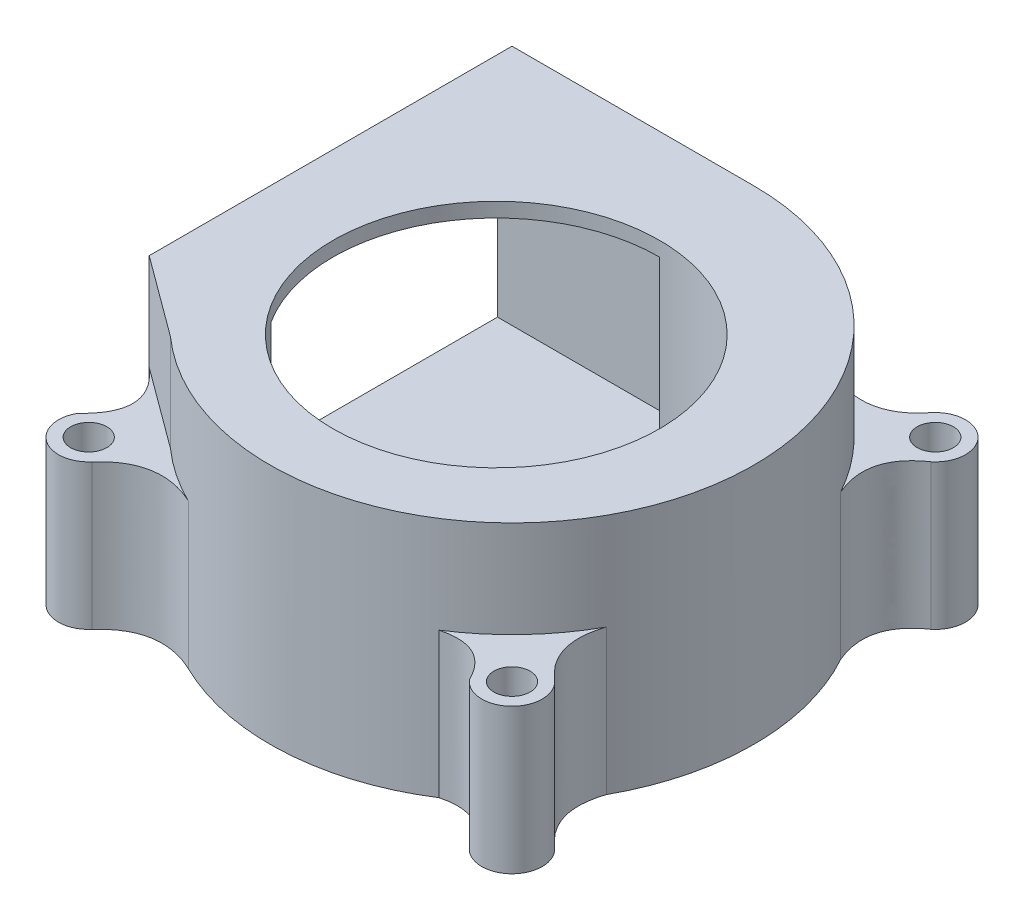
SolidWorks part; units mm, degrees
ref_plane "前视基准面" through (0, 0, 0) normal (0, 0, 1) x (1, 0, 0)
ref_plane "上视基准面" through (0, 0, 0) normal (0, 1, 0) x (1, 0, 0)
ref_plane "右视基准面" through (0, 0, 0) normal (1, 0, 0) x (0, 0, -1)
other "Configuration Table"
sketch "草图1" plane through (0, 0, 0) normal (0, 1, 0) x (1, 0, 0)
  line L1 (0, 0) -> (40, 0)
  line L2 (0, 0) -> (0, 40)
  line L3 (0, 40) -> (40, 40)
  line L4 (40, 0) -> (40, 40)
  circle A0 centre (2.5, 2.5) radius 1.5
  circle A1 centre (37.5, 2.5) radius 1.5
  circle A2 centre (37.5, 37.5) radius 1.5
  circle A4 centre (2.5, 37.5) radius 1.5 [skipped]
  dimension "D3" = 3
  dimension "D4" = 2.5
  dimension "D5" = 2.5
  dimension "D1" = 40
  dimension "D2" = 40
  dimension "D6" = 2
  dimension "D7" = 2
extrude "凸台-拉伸1" add sketch "草图1" along normal blind 20
sketch "草图2" plane through (0, 0, 0) normal (-1, 0, 0) x (0, 0, 1)
  line L0 (-40, 20) -> (-40, 0) construction
  line L1 (-11.5, 1.2) -> (-38.8, 1.2)
  line L2 (-11.5, 1.2) -> (-11.5, 18.8)
  line L3 (-11.5, 18.8) -> (-38.8, 18.8)
  line L4 (-38.8, 1.2) -> (-38.8, 18.8)
  line L5 (-40, 0) -> (0, 0) construction
  line L6 (-40, 20) -> (0, 20) construction
  dimension "D1" = 27.3
  dimension "D2" = 1.2
  dimension "D3" = 1.2
  dimension "D4" = 1.2
extrude "切除-拉伸1" cut sketch "草图2" against normal blind 20
sketch "草图3" plane through (0, 20, 0) normal (0, 1, 0) x (1, 0, 0)
  circle A0 centre (20, 18.7) radius 13.5
  circle A1 centre (2.5, 2.5) radius 1.5 construction
  circle A4 centre (37.5, 2.5) radius 1.5 construction
  point P8 (38.0337, 36.0982)
  dimension "D1" = 17.5
  dimension "D2" = 16.2
  dimension "D3" = 27
extrude "切除-拉伸2" cut sketch "草图3" against normal blind 18
sketch "草图4" plane through (0, 20, 0) normal (0, 1, 0) x (1, 0, 0)
  line L0 (20, 11.5) -> (20, 32.2) construction
  line L1 (20, 40) -> (0, 40)
  line L2 (0, 40) -> (0, 20)
  line L3 (0, 10) -> (6.6926, 5.0697)
  line L4 (0, 40) -> (0, 0) construction
  line L5 (0, 20) -> (0, 10)
  arc A0 (6.6926, 5.0697) -> (20, 40) centre (20, 20) ccw
  dimension "D1" = 30
extrude "切除-拉伸3" cut sketch "草图4" against normal blind 8 flip side to cut
sketch "草图5" plane through (0, 12, 0) normal (0, 1, 0) x (1, 0, 0)
  line L10 (0, 40) -> (0, 10)
  line L11 (20, 40) -> (0, 40)
  line L12 (0, 10) -> (6.6926, 5.0697)
  line L13 (0, 40) -> (0, 10)
  line L14 (20, 40) -> (0, 40)
  arc A0 (39.0764, 35.5597) -> (35.5993, 39.124) centre (37.5, 37.5) ccw
  arc A1 (35.5993, 0.876) -> (39.1801, 4.3513) centre (37.5, 2.5) ccw
  arc A2 (0.3398, 3.7584) -> (4.4007, 0.876) centre (2.5, 2.5) ccw
  arc A6 (37.5, 10.3175) -> (37.5, 29.6825) centre (20, 20) ccw
  arc A7 (6.6926, 5.0697) -> (20, 40) centre (20, 20) ccw
  arc A8 (11.2003, 2.0399) -> (30.7946, 3.1633) centre (20, 20) ccw
  arc A9 (29.6825, 37.5) -> (20, 40) centre (20, 20) ccw
  spline S0 degree 2 poles (0, 10) (3.6388, 6.8784) (0.3398, 3.7584) knots 0 0 0 1 1 1
  spline S1 degree 2 poles (11.2003, 2.0399) (7.1439, 3.9525) (4.4007, 0.876) knots 0 0 0 1 1 1
  spline S2 degree 2 poles (30.7946, 3.1633) (34.0639, 4.0359) (35.5993, 0.876) knots 0 0 0 1 1 1
  spline S3 degree 2 poles (37.5, 10.3175) (36.3198, 6.7657) (39.1801, 4.3513) knots 0 0 0 1 1 1
  spline S4 degree 2 poles (29.6825, 37.5) (33.3343, 36.2155) (35.5993, 39.124) knots 0 0 0 1 1 1
  spline S5 degree 2 poles (37.5, 29.6825) (35.9251, 33.3911) (39.0764, 35.5597) knots 0 0 0 1 1 1
  point P1 (0, 0)
  dimension "D1" = 0
extrude "切除-拉伸4" cut sketch "草图5" against normal through all flip side to cut
